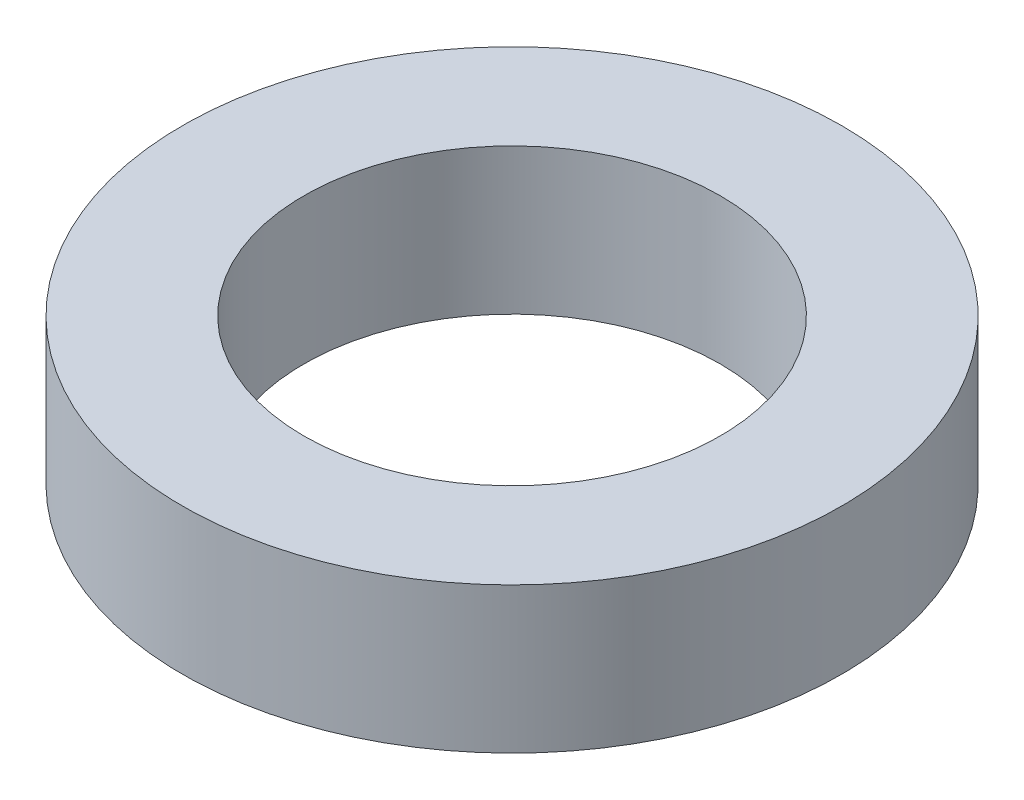
SolidWorks part; units mm, degrees
ref_plane "Front Plane" through (0, 0, 0) normal (0, 0, 1) x (1, 0, 0)
ref_plane "Top Plane" through (0, 0, 0) normal (0, 1, 0) x (1, 0, 0)
ref_plane "Right Plane" through (0, 0, 0) normal (1, 0, 0) x (0, 0, -1)
sketch "Sketch1" plane through (0, 0, 0) normal (0, 1, 0) x (1, 0, 0)
  circle A0 centre (0, 0) radius 47.5
  dimension "FLANGE_OD" = 95
extrude "Boss-Extrude1" add sketch "Sketch1" along normal blind 21
sketch "Sketch2" plane through (0, 0, 0) normal (0, 1, 0) x (1, 0, 0)
  circle A0 centre (0, 0) radius 30
  dimension "BORE_D" = 60
extrude "Cut-Extrude1" cut sketch "Sketch2" along normal through all
sketch "Sketch3" plane through (0, 21, 0) normal (0, 1, 0) x (1, 0, 0)
  circle A0 centre (0, 0) radius 17.0234 construction
  circle A1 centre (-17.0234, 0) radius 2.6255
  dimension "BOLT_D" = 5.251
  dimension "BOLT_PCD" = 34.0468
extrude "Cut-Extrude2" cut sketch "Sketch3" against normal blind 14.1732 rebuild error yes
pattern_circular "CirPattern1" count 5 over 360 rebuild error yes
